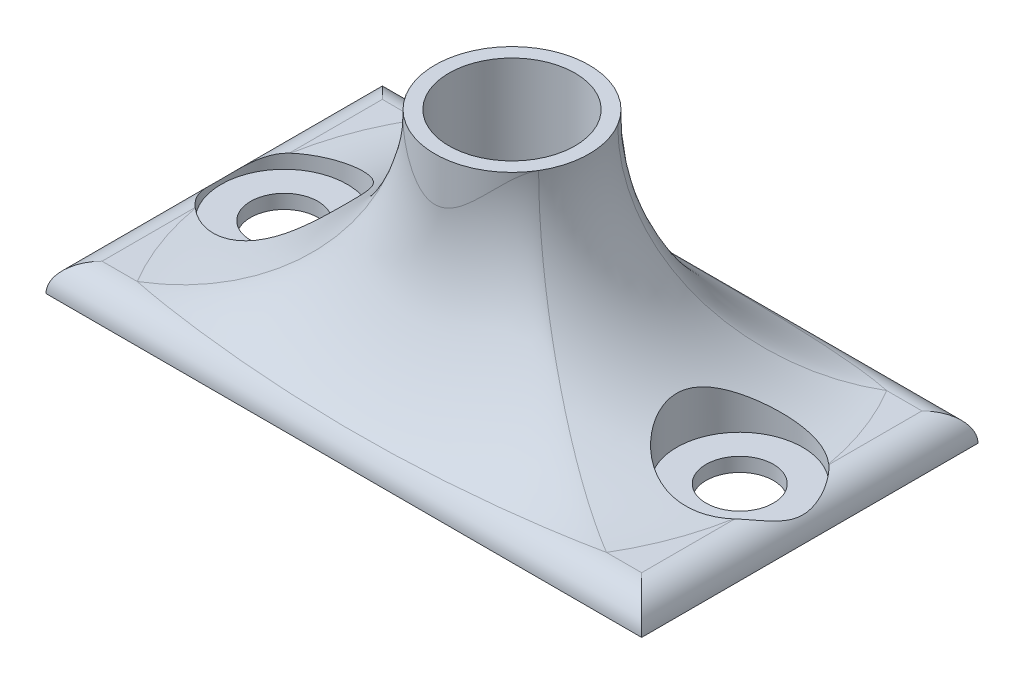
SolidWorks part; units mm, degrees
ref_plane "Front Plane" through (0, 0, 0) normal (0, 0, 1) x (1, 0, 0)
ref_plane "Top Plane" through (0, 0, 0) normal (0, 1, 0) x (1, 0, 0)
ref_plane "Right Plane" through (0, 0, 0) normal (1, 0, 0) x (0, 0, -1)
sketch "Sketch1" plane through (0, 0, 0) normal (0, 1, 0) x (1, 0, 0)
  line L0 (16.25, 0) -> (-16.25, 0) construction
  line L2 (21.25, 12) -> (-21.25, 12)
  line L3 (21.25, 12) -> (21.25, -12)
  line L4 (21.25, -12) -> (-21.25, -12)
  line L5 (-21.25, 12) -> (-21.25, -12)
  line L6 (21.25, 12) -> (-21.25, -12) construction
  line L7 (21.25, -12) -> (-21.25, 12) construction
  circle A3 centre (0, 0) radius 4.5
  circle A4 centre (16.25, 0) radius 4.5
  circle A5 centre (-16.25, 0) radius 4.5
  point P0 (0, 0)
  point P4 (0, 0)
  dimension "D2" = 24
  dimension "D4" = 9
  dimension "D5" = 9
  dimension "D1" = 32.5
  dimension "D3" = 42.5
extrude "Boss-Extrude1" add sketch "Sketch1" along normal blind 2
extrude "Boss-Extrude2" add sketch "Sketch1<2>" along normal blind 1 contours A4 | A5 region at (16.25, 0, 0) region at (-16.25, 0, 0)
sketch "Sketch1<2>" plane through (0, 0, 0) normal (0, 1, 0) x (1, 0, 0) same geometry as "Sketch1"
sketch "Sketch2" plane through (0, 0, 0) normal (0, 0, 1) x (1, 0, 0)
  line L0 (-21.25, 2) -> (21.25, 2) construction
  line L1 (-5.5, 2) -> (-4.5, 2)
  line L2 (-5.5, 2) -> (-5.5, 16)
  line L3 (-5.5, 16) -> (-4.5, 16)
  line L4 (-4.5, 2) -> (-4.5, 16)
  line L5 (0, 0) -> (0, 50000) construction
  dimension "D1" = 4.5
  dimension "D2" = 5.5
  dimension "D3" = 14
revolve "Revolve1" add sketch "Sketch2" angle 360 about L5
fillet "Fillet3" radius 2 4 edges at (0, 2, 12) (0, 2, -12) (21.25, 2, 0) (-21.25, 2, 0)
fillet "Fillet2" radius 14 1 edges at (0, 2, -5.5)
chamfer "Chamfer1" [suppressed] distance 3 angle 45
hole_wizard "M4 Clearance Hole1" positions "Sketch3" profile "Sketch4" hole size "M4" standard "ANSI Metric" end condition through all
sketch "Sketch3" plane through (0, 0, 0) normal (0, -1, 0) x (-1, 0, 0)
  point P0 (-16.25, 0)
  point P3 (16.25, 0)
sketch "Sketch4" plane through (16.25, 0, 0) normal (1, 0, 0) x (0, 0, -1)
  line L0 (0, 0) -> (0, 16.4554)
  line L1 (0, 16.4554) -> (2.4, 16.4554)
  line L2 (2.4, 16.4554) -> (2.4, 0)
  line L5 (2.4, 0) -> (0, 0)
  line L11 (0, -6.35) -> (0, 107.95) construction
  dimension "Thru Hole Dia." = 4.8
  dimension "Thru Hole Depth" = 16.4554
